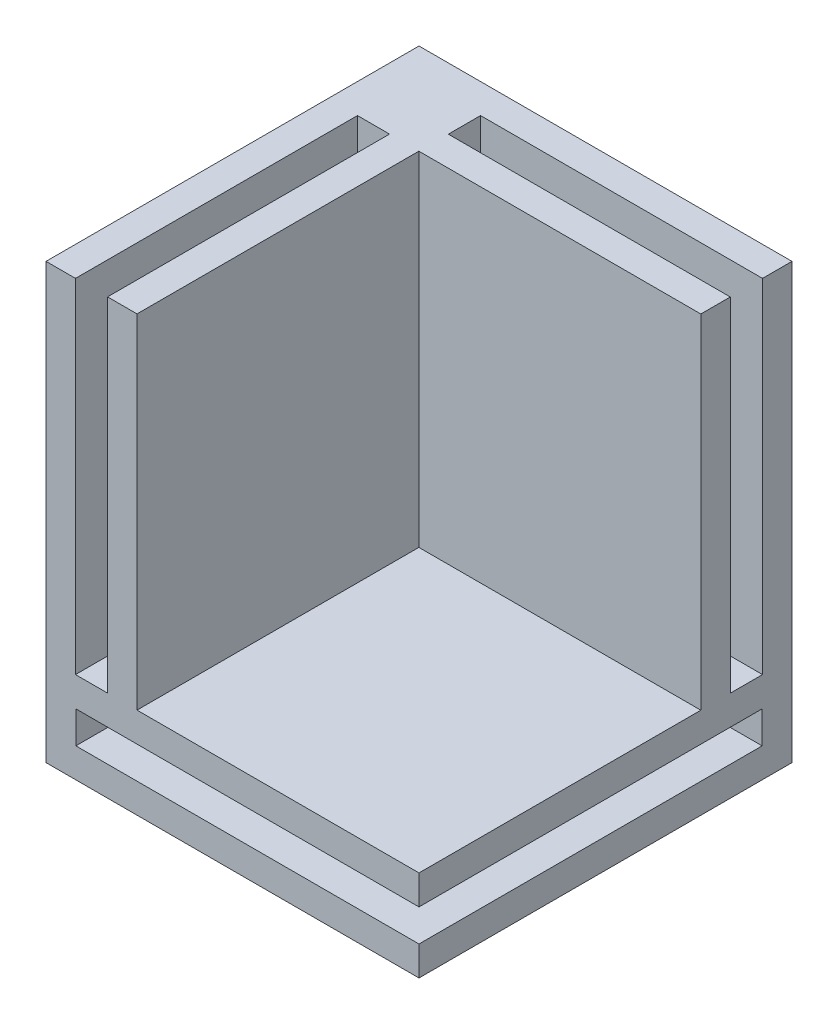
SolidWorks part; units mm, degrees
ref_plane "Plan de face" through (0, 0, 0) normal (0, 0, 1) x (1, 0, 0)
ref_plane "Plan de dessus" through (0, 0, 0) normal (0, 1, 0) x (1, 0, 0)
ref_plane "Plan de droite" through (0, 0, 0) normal (1, 0, 0) x (0, 0, -1)
sketch "Sketch1" plane through (0, 0, 0) normal (0, 0, 1) x (1, 0, 0)
  line L1 (-41.2499, 24.2978) -> (8.7501, 24.2978)
  line L2 (-41.2499, 24.2978) -> (-41.2499, 12.0978)
  line L3 (-41.2499, 12.0978) -> (8.7501, 12.0978)
  line L4 (8.7501, 24.2978) -> (8.7501, 12.0978)
  dimension "D1" = 12.2
  dimension "D2" = 50
extrude "Boss-Extrude1" add sketch "Sketch1" along normal blind 50
sketch "Sketch2" plane through (8.7501, 0, 0) normal (1, 0, 0) x (0, 0, -1)
  line L0 (-50, 12.0978) -> (-50, 24.2978) construction
  line L1 (-50, 20.3478) -> (-4, 20.3478)
  line L2 (-50, 20.3478) -> (-50, 16.0478)
  line L3 (-50, 16.0478) -> (-4, 16.0478)
  line L4 (-4, 20.3478) -> (-4, 16.0478)
  line L5 (-50, 24.2978) -> (0, 24.2978) construction
  line L6 (-50, 12.0978) -> (0, 12.0978) construction
  line L7 (0, 12.0978) -> (0, 24.2978) construction
  dimension "D1" = 3.95
  dimension "D2" = 3.95
  dimension "D3" = 4.3
  dimension "D4" = 4
extrude "Cut-Extrude1" cut sketch "Sketch2" against normal blind 46
sketch "Sketch3" plane through (0, 24.2978, 0) normal (0, 1, 0) x (1, 0, 0)
  line L1 (-41.2499, 0) -> (8.7501, 0)
  line L2 (-41.2499, 0) -> (-41.2499, -50)
  line L3 (-41.2499, -50) -> (8.7501, -50)
  line L4 (8.7501, 0) -> (8.7501, -50)
extrude "Boss-Extrude2" add sketch "Sketch3" along normal blind 46
sketch "Sketch4" plane through (0, 70.2978, 0) normal (0, 1, 0) x (1, 0, 0)
  line L0 (-41.2499, 0) -> (-41.2499, -50) construction
  line L1 (8.7501, -50) -> (-29.0499, -50)
  line L2 (8.7501, -50) -> (8.7501, -12.22)
  line L3 (8.7501, -12.22) -> (-29.0499, -12.22)
  line L4 (-29.0499, -50) -> (-29.0499, -12.22)
  line L5 (8.7501, 0) -> (-41.2499, 0) construction
  dimension "D1" = 12.2
  dimension "D2" = 12.22
extrude "Cut-Extrude2" cut sketch "Sketch4" against normal blind 46
sketch "Sketch6" plane through (8.7501, 0, 0) normal (1, 0, 0) x (0, 0, -1)
  line L0 (-12.22, 70.2978) -> (0, 70.2978) construction
  line L1 (-8.27, 70.2978) -> (-3.95, 70.2978)
  line L2 (-8.27, 70.2978) -> (-8.27, 24.2978)
  line L3 (-8.27, 24.2978) -> (-3.95, 24.2978)
  line L4 (-3.95, 70.2978) -> (-3.95, 24.2978)
  line L5 (0, 12.0978) -> (0, 70.2978) construction
  line L6 (-12.22, 24.2978) -> (-12.22, 70.2978) construction
  dimension "D1" = 46
  dimension "D2" = 3.95
  dimension "D3" = 3.95
extrude "Cut-Extrude3" cut sketch "Sketch6" against normal blind 37.8
sketch "Sketch9" plane through (0, 0, 50) normal (0, 0, 1) x (1, 0, 0)
  line L0 (-41.2499, 70.2978) -> (-29.0499, 70.2978) construction
  line L1 (-37.2999, 70.2978) -> (-32.9999, 70.2978)
  line L2 (-37.2999, 70.2978) -> (-37.2999, 24.2978)
  line L3 (-37.2999, 24.2978) -> (-32.9999, 24.2978)
  line L4 (-32.9999, 70.2978) -> (-32.9999, 24.2978)
  line L5 (-41.2499, 70.2978) -> (-41.2499, 12.0978) construction
  line L6 (-29.0499, 24.2978) -> (-29.0499, 70.2978) construction
  dimension "D1" = 46
  dimension "D2" = 3.95
  dimension "D3" = 3.95
extrude "Cut-Extrude4" cut sketch "Sketch9" against normal blind 37.8
